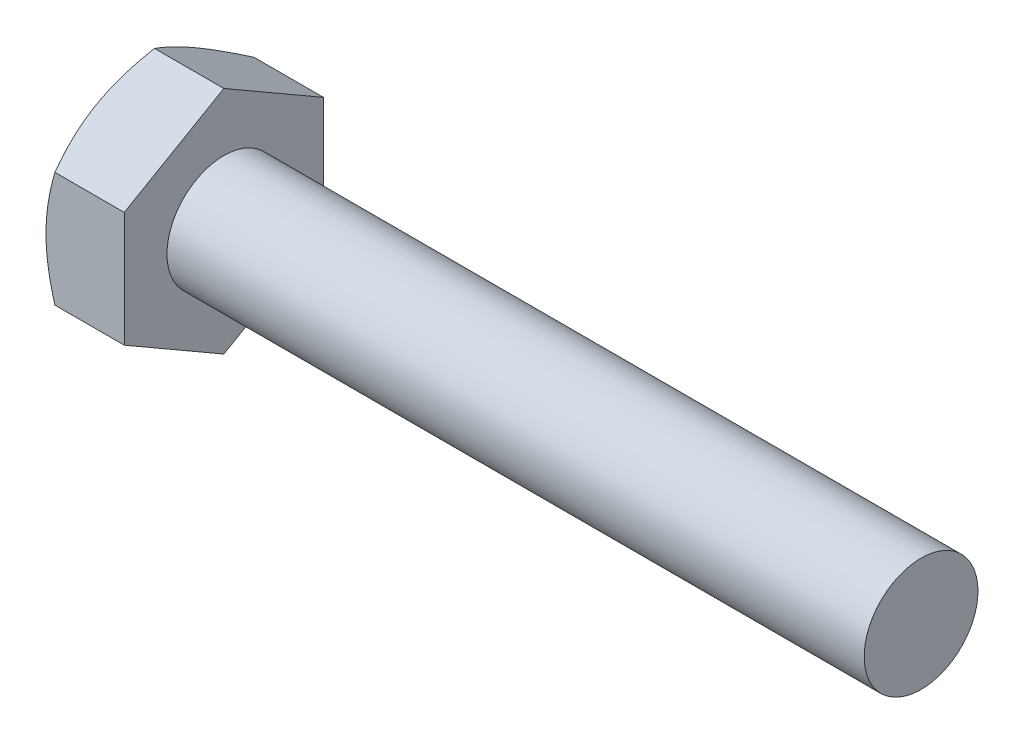
SolidWorks part; units mm, degrees
material "AISI 1020"
ref_plane "Front Plane" through (0, 0, 0) normal (0, 0, 1) x (1, 0, 0)
ref_plane "Top Plane" through (0, 0, 0) normal (0, 1, 0) x (1, 0, 0)
ref_plane "Right Plane" through (0, 0, 0) normal (1, 0, 0) x (0, 0, -1)
sketch "Sketch1" plane through (0, 0, 0) normal (0, 0, 1) x (1, 0, 0)
  line L0 (-21.6297, 0) -> (21.6297, 0) construction
  line L1 (21.6297, 3.175) -> (21.6297, -3.175) construction
  line L2 (-17.2641, 5.5562) -> (-17.2641, -5.5562) construction
  line L3 (-21.6297, 5.5562) -> (-21.6297, -5.5562) construction
  point P9 (-17.2641, 0)
  point P10 (18.4547, -3.175)
  point P11 (9.7234, 0)
  dimension "D1" = 3.175
ref_plane "Plane2" through (21.6297, 0, 0) normal (1, 0, 0) x (0, 0, -1)
sketch "Sketch5" plane through (21.6297, 0, 0) normal (1, 0, 0) x (0, 0, -1)
  circle A0 centre (0, 0) radius 3.175
extrude "Boss-Extrude3" add sketch "Sketch5" against normal up to vertex (38.8937 mm away) up to point (-17.2641, 0, 0)
sketch "Sketch6" plane through (-17.2641, 0, 0) normal (-1, 0, 0) x (0, 0, 1)
  line L0 (0, 5.5562) -> (0, -5.5562) construction
  line L1 (5.5562, 3.2079) -> (0, 6.4158)
  line L2 (0, 6.4158) -> (-5.5563, 3.2079)
  line L3 (-5.5563, 3.2079) -> (-5.5563, -3.2079)
  line L4 (-5.5563, -3.2079) -> (0, -6.4158)
  line L5 (0, -6.4158) -> (5.5563, -3.2079)
  line L6 (5.5563, -3.2079) -> (5.5562, 3.2079)
  circle A0 centre (0, 0) radius 5.5562 construction
extrude "Boss-Extrude4" add sketch "Sketch6" along normal up to vertex (4.3656 mm away) up to point (-21.6297, -5.5562, 0)
sketch "Sketch7" plane through (-21.6297, 0, 0) normal (-1, 0, 0) x (0, 0, 1)
  circle A0 centre (0, 0) radius 5.5562 construction
  circle A1 centre (0, 0) radius 5.5562
sketch "Sketch12" plane through (-21.6297, 0, 0) normal (-1, 0, 0) x (0, 0, 1)
  line L0 (0, 4.2783) -> (0, 2.3892) construction
  line L1 (0.1667, 4.2783) -> (0.1667, 2.3892)
  line L2 (-0.1667, 4.2783) -> (-0.1667, 2.3892)
  line L3 (0, 3.175) -> (0, -3.175) construction
  arc A0 (0.1667, 4.2783) -> (-0.1667, 4.2783) centre (0, 4.2783) ccw
  arc A1 (-0.1667, 2.3892) -> (0.1667, 2.3892) centre (0, 2.3892) ccw
  circle A3 centre (0, 0) radius 2.2225 construction
  circle A4 centre (0, 0) radius 4.445 construction
  point P2 (0, 3.3337)
  dimension "D1" = 4.445
  dimension "D3" = 8.89
  dimension "D2" = 0.3334
sketch "Sketch8" plane through (-21.6297, 0, 0) normal (-1, 0, 0) x (0, 0, 1)
  circle A0 centre (0, 0) radius 5.5562 construction
  circle A1 centre (0, 0) radius 5.5562
extrude "Cut-Extrude3" cut sketch "Sketch8" against normal through all draft 60 flip side to cut
ref_plane "Split Plane" through (9.7234, 0, 0) normal (1, 0, 0) x (0, 0, -1)
ref_axis "Center Axis 1" through (-21.6297, 0, 0) along (1, 0, 0)
ref_plane "Contact Plane 1" through (-17.2641, 0, 0) normal (1, 0, 0) x (0, 0, -1)
split "Split1" [suppressed] bodies to split 113
sketch "Sketch9" [suppressed] plane through (21.6297, 0, 0) normal (1, 0, 0) x (0, 0, -1)
  circle A1 centre (0, 0) radius 3.175
  circle A2 centre (0, 0) radius 3.175
  dimension "D1" = 0
curve "Helix/Spiral1" [suppressed] pitch 0.9071 height 12.8134 turns 14.125 parameters "Pitch"=0.9071
chamfer "Chamfer1" [suppressed] distance 0.6804 angle 45
sketch "Sketch10" [suppressed] plane through (0, 0, 0) normal (0, 0, 1) x (1, 0, 0)
  line L0 (21.6297, 3.175) -> (21.9699, 2.5858)
  line L1 (21.9699, 2.5858) -> (22.0833, 2.5858)
  line L2 (22.0833, 2.5858) -> (22.4234, 3.175)
  line L3 (21.6297, 3.175) -> (22.4234, 3.175)
  line L4 (22.0266, 3.175) -> (22.0266, 2.5858) construction
  line L5 (21.7998, 2.8804) -> (22.2533, 2.8804) construction
  dimension "D1" = 60
  dimension "D2" = 0.1134
  dimension "D3" = 0.4536
sweep "Cut-Sweep1" [suppressed] cut profiles "Sketch10" path "Helix/Spiral1"
sketch "Sketch15" [suppressed] plane through (9.7234, 0, 0) normal (1, 0, 0) x (0, 0, -1)
  circle A0 centre (0, 0) radius 3.175 construction
  circle A1 centre (0, 0) radius 3.175
extrude "Boss-Extrude5" [suppressed] add sketch "Sketch15" along normal through all draft 40
equation "\"D2@Sketch10\" = \"Pitch@Helix/Spiral1\"*.125"
equation "\"D3@Sketch10\" = \"Pitch@Helix/Spiral1\"*.5"
equation "\"D3@Helix/Spiral1\"=\"Min Thread@Sketch1\"+\"Pitch@Helix/Spiral1\""
equation "\"D1@Chamfer1\" = \"Pitch@Helix/Spiral1\"*.75"
equation "\"D1@Sketch12\" = \"Hex@Sketch1\"*.4"
equation "\"D3@Sketch12\" = \"Hex@Sketch1\"*.8"
equation "\"D2@Sketch12\" = \"Hex@Sketch1\"*.03"
equation "\"D1@Sketch1\" = \"Pitch@Helix/Spiral1\"*3.5"
